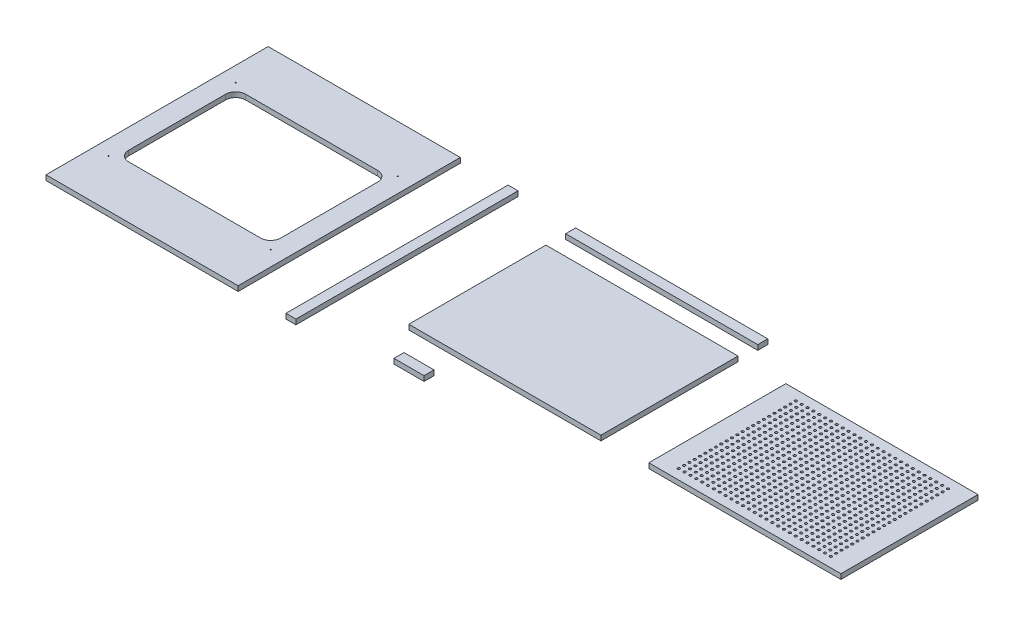
SolidWorks part; units mm, degrees
ref_plane "Front Plane" through (0, 0, 0) normal (0, 0, 1) x (1, 0, 0)
ref_plane "Top Plane" through (0, 0, 0) normal (0, 1, 0) x (1, 0, 0)
ref_plane "Right Plane" through (0, 0, 0) normal (1, 0, 0) x (0, 0, -1)
sketch "Sketch1" plane through (0, 0, 0) normal (0, 1, 0) x (1, 0, 0)
  line L0 (-192, -117) -> (192, -117)
  line L5 (-192, -222) -> (192, -222)
  line L6 (-192, -222) -> (-192, 222)
  line L7 (-192, 222) -> (192, 222)
  line L8 (192, -222) -> (192, 222)
  line L9 (-192, -222) -> (192, 222) construction
  line L10 (-192, 222) -> (192, -222) construction
  line L11 (192, 117) -> (-192, 117)
  line L12 (0, 117) -> (0, 222) construction
  line L13 (0, -117) -> (0, -222) construction
  line L14 (-152, 117) -> (-152, -117)
  line L15 (152, -117) -> (152, 117)
  line L16 (152, 0) -> (192, 0) construction
  line L17 (-152, 0) -> (-192, 0) construction
  line L18 (1292.7699, 155.8922) -> (908.7699, -118.1078) construction
  line L19 (-152, 117) -> (-162, 117) construction
  line L20 (-152, 117) -> (-152, 127) construction
  line L21 (-152, 127) -> (-162, 127) construction
  line L22 (-162, 117) -> (-162, 127) construction
  line L23 (813.2094, -118.1078) -> (429.2094, -118.1078)
  line L24 (813.2094, -118.1078) -> (813.2094, 155.8922)
  line L25 (813.2094, 155.8922) -> (429.2094, 155.8922)
  line L26 (429.2094, -118.1078) -> (429.2094, 155.8922)
  line L27 (813.2094, -118.1078) -> (429.2094, 155.8922) construction
  line L28 (813.2094, 155.8922) -> (429.2094, -118.1078) construction
  line L29 (287.48, 222) -> (307.48, 222)
  line L30 (287.48, 222) -> (287.48, -222)
  line L31 (287.48, -222) -> (307.48, -222)
  line L32 (307.48, 222) -> (307.48, -222)
  line L33 (429.2094, 195.3549) -> (813.2094, 195.3549)
  line L34 (429.2094, 195.3549) -> (429.2094, 215.3549)
  line L35 (429.2094, 215.3549) -> (813.2094, 215.3549)
  line L36 (813.2094, 195.3549) -> (813.2094, 215.3549)
  line L37 (473.4153, -171.9532) -> (533.4153, -171.9532)
  line L38 (473.4153, -171.9532) -> (473.4153, -191.9532)
  line L39 (473.4153, -191.9532) -> (533.4153, -191.9532)
  line L40 (533.4153, -171.9532) -> (533.4153, -191.9532)
  line L41 (908.7699, 155.8922) -> (1292.7699, 155.8922)
  line L42 (908.7699, 155.8922) -> (908.7699, -118.1078)
  line L43 (908.7699, -118.1078) -> (1292.7699, -118.1078)
  line L44 (1292.7699, 155.8922) -> (1292.7699, -118.1078)
  line L45 (908.7699, 155.8922) -> (1292.7699, -118.1078) construction
  line L46 (-162, -127) -> (0, -127) construction
  line L47 (0, -127) -> (0, 0) construction
  line L48 (-152, 0) -> (152, 0) construction
  line L49 (948.7699, 18.8922) -> (1252.7699, 18.8922) construction
  line L50 (948.7699, 135.8922) -> (948.7699, -98.1078) construction
  circle A0 centre (-162, 127) radius 1
  circle A1 centre (162, 127) radius 1
  circle A2 centre (162, -127) radius 1
  circle A3 centre (-162, -127) radius 1
  circle A4 centre (948.7699, -98.1078) radius 2.4
  circle A5 centre (960.4622, -98.1078) radius 2.4
  circle A6 centre (972.1545, -98.1078) radius 2.4
  circle A7 centre (983.8468, -98.1078) radius 2.4
  circle A8 centre (995.5391, -98.1078) radius 2.4
  circle A9 centre (1007.2314, -98.1078) radius 2.4
  circle A10 centre (1018.9237, -98.1078) radius 2.4
  circle A11 centre (1030.616, -98.1078) radius 2.4
  circle A12 centre (1042.3083, -98.1078) radius 2.4
  circle A13 centre (1054.0007, -98.1078) radius 2.4
  circle A14 centre (1065.693, -98.1078) radius 2.4
  circle A15 centre (1077.3853, -98.1078) radius 2.4
  circle A16 centre (1089.0776, -98.1078) radius 2.4
  circle A17 centre (1100.7699, -98.1078) radius 2.4
  circle A18 centre (1112.4622, -98.1078) radius 2.4
  circle A19 centre (1124.1545, -98.1078) radius 2.4
  circle A20 centre (1135.8468, -98.1078) radius 2.4
  circle A21 centre (1147.5391, -98.1078) radius 2.4
  circle A22 centre (1159.2314, -98.1078) radius 2.4
  circle A23 centre (1170.9237, -98.1078) radius 2.4
  circle A24 centre (1182.616, -98.1078) radius 2.4
  circle A25 centre (1194.3083, -98.1078) radius 2.4
  circle A26 centre (1206.0007, -98.1078) radius 2.4
  circle A27 centre (1217.693, -98.1078) radius 2.4
  circle A28 centre (1229.3853, -98.1078) radius 2.4
  circle A29 centre (1241.0776, -98.1078) radius 2.4
  circle A30 centre (1252.7699, -98.1078) radius 2.4
  circle A31 centre (960.4622, -87.4714) radius 2.4
  circle A32 centre (972.1545, -87.4714) radius 2.4
  circle A33 centre (983.8468, -87.4714) radius 2.4
  circle A34 centre (995.5391, -87.4714) radius 2.4
  circle A35 centre (1007.2314, -87.4714) radius 2.4
  circle A36 centre (1018.9237, -87.4714) radius 2.4
  circle A37 centre (1030.616, -87.4714) radius 2.4
  circle A38 centre (1042.3083, -87.4714) radius 2.4
  circle A39 centre (1054.0007, -87.4714) radius 2.4
  circle A40 centre (1065.693, -87.4714) radius 2.4
  circle A41 centre (1077.3853, -87.4714) radius 2.4
  circle A42 centre (1089.0776, -87.4714) radius 2.4
  circle A43 centre (1100.7699, -87.4714) radius 2.4
  circle A44 centre (1112.4622, -87.4714) radius 2.4
  circle A45 centre (1124.1545, -87.4714) radius 2.4
  circle A46 centre (1135.8468, -87.4714) radius 2.4
  circle A47 centre (1147.5391, -87.4714) radius 2.4
  circle A48 centre (1159.2314, -87.4714) radius 2.4
  circle A49 centre (1170.9237, -87.4714) radius 2.4
  circle A50 centre (1182.616, -87.4714) radius 2.4
  circle A51 centre (1194.3083, -87.4714) radius 2.4
  circle A52 centre (1206.0007, -87.4714) radius 2.4
  circle A53 centre (1217.693, -87.4714) radius 2.4
  circle A54 centre (1229.3853, -87.4714) radius 2.4
  circle A55 centre (1241.0776, -87.4714) radius 2.4
  circle A56 centre (1252.7699, -87.4714) radius 2.4
  circle A57 centre (960.4622, -76.835) radius 2.4
  circle A58 centre (972.1545, -76.835) radius 2.4
  circle A59 centre (983.8468, -76.835) radius 2.4
  circle A60 centre (995.5391, -76.835) radius 2.4
  circle A61 centre (1007.2314, -76.835) radius 2.4
  circle A62 centre (1018.9237, -76.835) radius 2.4
  circle A63 centre (1030.616, -76.835) radius 2.4
  circle A64 centre (1042.3083, -76.835) radius 2.4
  circle A65 centre (1054.0007, -76.835) radius 2.4
  circle A66 centre (1065.693, -76.835) radius 2.4
  circle A67 centre (1077.3853, -76.835) radius 2.4
  circle A68 centre (1089.0776, -76.835) radius 2.4
  circle A69 centre (1100.7699, -76.835) radius 2.4
  circle A70 centre (1112.4622, -76.835) radius 2.4
  circle A71 centre (1124.1545, -76.835) radius 2.4
  circle A72 centre (1135.8468, -76.835) radius 2.4
  circle A73 centre (1147.5391, -76.835) radius 2.4
  circle A74 centre (1159.2314, -76.835) radius 2.4
  circle A75 centre (1170.9237, -76.835) radius 2.4
  circle A76 centre (1182.616, -76.835) radius 2.4
  circle A77 centre (1194.3083, -76.835) radius 2.4
  circle A78 centre (1206.0007, -76.835) radius 2.4
  circle A79 centre (1217.693, -76.835) radius 2.4
  circle A80 centre (1229.3853, -76.835) radius 2.4
  circle A81 centre (1241.0776, -76.835) radius 2.4
  circle A82 centre (1252.7699, -76.835) radius 2.4
  circle A83 centre (960.4622, -66.1987) radius 2.4
  circle A84 centre (972.1545, -66.1987) radius 2.4
  circle A85 centre (983.8468, -66.1987) radius 2.4
  circle A86 centre (995.5391, -66.1987) radius 2.4
  circle A87 centre (1007.2314, -66.1987) radius 2.4
  circle A88 centre (1018.9237, -66.1987) radius 2.4
  circle A89 centre (1030.616, -66.1987) radius 2.4
  circle A90 centre (1042.3083, -66.1987) radius 2.4
  circle A91 centre (1054.0007, -66.1987) radius 2.4
  circle A92 centre (1065.693, -66.1987) radius 2.4
  circle A93 centre (1077.3853, -66.1987) radius 2.4
  circle A94 centre (1089.0776, -66.1987) radius 2.4
  circle A95 centre (1100.7699, -66.1987) radius 2.4
  circle A96 centre (1112.4622, -66.1987) radius 2.4
  circle A97 centre (1124.1545, -66.1987) radius 2.4
  circle A98 centre (1135.8468, -66.1987) radius 2.4
  circle A99 centre (1147.5391, -66.1987) radius 2.4
  circle A100 centre (1159.2314, -66.1987) radius 2.4
  circle A101 centre (1170.9237, -66.1987) radius 2.4
  circle A102 centre (1182.616, -66.1987) radius 2.4
  circle A103 centre (1194.3083, -66.1987) radius 2.4
  circle A104 centre (1206.0007, -66.1987) radius 2.4
  circle A105 centre (1217.693, -66.1987) radius 2.4
  circle A106 centre (1229.3853, -66.1987) radius 2.4
  circle A107 centre (1241.0776, -66.1987) radius 2.4
  circle A108 centre (1252.7699, -66.1987) radius 2.4
  circle A109 centre (960.4622, -55.5623) radius 2.4
  circle A110 centre (972.1545, -55.5623) radius 2.4
  circle A111 centre (983.8468, -55.5623) radius 2.4
  circle A112 centre (995.5391, -55.5623) radius 2.4
  circle A113 centre (1007.2314, -55.5623) radius 2.4
  circle A114 centre (1018.9237, -55.5623) radius 2.4
  circle A115 centre (1030.616, -55.5623) radius 2.4
  circle A116 centre (1042.3083, -55.5623) radius 2.4
  circle A117 centre (1054.0007, -55.5623) radius 2.4
  circle A118 centre (1065.693, -55.5623) radius 2.4
  circle A119 centre (1077.3853, -55.5623) radius 2.4
  circle A120 centre (1089.0776, -55.5623) radius 2.4
  circle A121 centre (1100.7699, -55.5623) radius 2.4
  circle A122 centre (1112.4622, -55.5623) radius 2.4
  circle A123 centre (1124.1545, -55.5623) radius 2.4
  circle A124 centre (1135.8468, -55.5623) radius 2.4
  circle A125 centre (1147.5391, -55.5623) radius 2.4
  circle A126 centre (1159.2314, -55.5623) radius 2.4
  circle A127 centre (1170.9237, -55.5623) radius 2.4
  circle A128 centre (1182.616, -55.5623) radius 2.4
  circle A129 centre (1194.3083, -55.5623) radius 2.4
  circle A130 centre (1206.0007, -55.5623) radius 2.4
  circle A131 centre (1217.693, -55.5623) radius 2.4
  circle A132 centre (1229.3853, -55.5623) radius 2.4
  circle A133 centre (1241.0776, -55.5623) radius 2.4
  circle A134 centre (1252.7699, -55.5623) radius 2.4
  circle A135 centre (960.4622, -44.9259) radius 2.4
  circle A136 centre (972.1545, -44.9259) radius 2.4
  circle A137 centre (983.8468, -44.9259) radius 2.4
  circle A138 centre (995.5391, -44.9259) radius 2.4
  circle A139 centre (1007.2314, -44.9259) radius 2.4
  circle A140 centre (1018.9237, -44.9259) radius 2.4
  circle A141 centre (1030.616, -44.9259) radius 2.4
  circle A142 centre (1042.3083, -44.9259) radius 2.4
  circle A143 centre (1054.0007, -44.9259) radius 2.4
  circle A144 centre (1065.693, -44.9259) radius 2.4
  circle A145 centre (1077.3853, -44.9259) radius 2.4
  circle A146 centre (1089.0776, -44.9259) radius 2.4
  circle A147 centre (1100.7699, -44.9259) radius 2.4
  circle A148 centre (1112.4622, -44.9259) radius 2.4
  circle A149 centre (1124.1545, -44.9259) radius 2.4
  circle A150 centre (1135.8468, -44.9259) radius 2.4
  circle A151 centre (1147.5391, -44.9259) radius 2.4
  circle A152 centre (1159.2314, -44.9259) radius 2.4
  circle A153 centre (1170.9237, -44.9259) radius 2.4
  circle A154 centre (1182.616, -44.9259) radius 2.4
  circle A155 centre (1194.3083, -44.9259) radius 2.4
  circle A156 centre (1206.0007, -44.9259) radius 2.4
  circle A157 centre (1217.693, -44.9259) radius 2.4
  circle A158 centre (1229.3853, -44.9259) radius 2.4
  circle A159 centre (1241.0776, -44.9259) radius 2.4
  circle A160 centre (1252.7699, -44.9259) radius 2.4
  circle A161 centre (960.4622, -34.2896) radius 2.4
  circle A162 centre (972.1545, -34.2896) radius 2.4
  circle A163 centre (983.8468, -34.2896) radius 2.4
  circle A164 centre (995.5391, -34.2896) radius 2.4
  circle A165 centre (1007.2314, -34.2896) radius 2.4
  circle A166 centre (1018.9237, -34.2896) radius 2.4
  circle A167 centre (1030.616, -34.2896) radius 2.4
  circle A168 centre (1042.3083, -34.2896) radius 2.4
  circle A169 centre (1054.0007, -34.2896) radius 2.4
  circle A170 centre (1065.693, -34.2896) radius 2.4
  circle A171 centre (1077.3853, -34.2896) radius 2.4
  circle A172 centre (1089.0776, -34.2896) radius 2.4
  circle A173 centre (1100.7699, -34.2896) radius 2.4
  circle A174 centre (1112.4622, -34.2896) radius 2.4
  circle A175 centre (1124.1545, -34.2896) radius 2.4
  circle A176 centre (1135.8468, -34.2896) radius 2.4
  circle A177 centre (1147.5391, -34.2896) radius 2.4
  circle A178 centre (1159.2314, -34.2896) radius 2.4
  circle A179 centre (1170.9237, -34.2896) radius 2.4
  circle A180 centre (1182.616, -34.2896) radius 2.4
  circle A181 centre (1194.3083, -34.2896) radius 2.4
  circle A182 centre (1206.0007, -34.2896) radius 2.4
  circle A183 centre (1217.693, -34.2896) radius 2.4
  circle A184 centre (1229.3853, -34.2896) radius 2.4
  circle A185 centre (1241.0776, -34.2896) radius 2.4
  circle A186 centre (1252.7699, -34.2896) radius 2.4
  circle A187 centre (960.4622, -23.6532) radius 2.4
  circle A188 centre (972.1545, -23.6532) radius 2.4
  circle A189 centre (983.8468, -23.6532) radius 2.4
  circle A190 centre (995.5391, -23.6532) radius 2.4
  circle A191 centre (1007.2314, -23.6532) radius 2.4
  circle A192 centre (1018.9237, -23.6532) radius 2.4
  circle A193 centre (1030.616, -23.6532) radius 2.4
  circle A194 centre (1042.3083, -23.6532) radius 2.4
  circle A195 centre (1054.0007, -23.6532) radius 2.4
  circle A196 centre (1065.693, -23.6532) radius 2.4
  circle A197 centre (1077.3853, -23.6532) radius 2.4
  circle A198 centre (1089.0776, -23.6532) radius 2.4
  circle A199 centre (1100.7699, -23.6532) radius 2.4
  circle A200 centre (1112.4622, -23.6532) radius 2.4
  circle A201 centre (1124.1545, -23.6532) radius 2.4
  circle A202 centre (1135.8468, -23.6532) radius 2.4
  circle A203 centre (1147.5391, -23.6532) radius 2.4
  circle A204 centre (1159.2314, -23.6532) radius 2.4
  circle A205 centre (1170.9237, -23.6532) radius 2.4
  circle A206 centre (1182.616, -23.6532) radius 2.4
  circle A207 centre (1194.3083, -23.6532) radius 2.4
  circle A208 centre (1206.0007, -23.6532) radius 2.4
  circle A209 centre (1217.693, -23.6532) radius 2.4
  circle A210 centre (1229.3853, -23.6532) radius 2.4
  circle A211 centre (1241.0776, -23.6532) radius 2.4
  circle A212 centre (1252.7699, -23.6532) radius 2.4
  circle A213 centre (960.4622, -13.0169) radius 2.4
  circle A214 centre (972.1545, -13.0169) radius 2.4
  circle A215 centre (983.8468, -13.0169) radius 2.4
  circle A216 centre (995.5391, -13.0169) radius 2.4
  circle A217 centre (1007.2314, -13.0169) radius 2.4
  circle A218 centre (1018.9237, -13.0169) radius 2.4
  circle A219 centre (1030.616, -13.0169) radius 2.4
  circle A220 centre (1042.3083, -13.0169) radius 2.4
  circle A221 centre (1054.0007, -13.0169) radius 2.4
  circle A222 centre (1065.693, -13.0169) radius 2.4
  circle A223 centre (1077.3853, -13.0169) radius 2.4
  circle A224 centre (1089.0776, -13.0169) radius 2.4
  circle A225 centre (1100.7699, -13.0169) radius 2.4
  circle A226 centre (1112.4622, -13.0169) radius 2.4
  circle A227 centre (1124.1545, -13.0169) radius 2.4
  circle A228 centre (1135.8468, -13.0169) radius 2.4
  circle A229 centre (1147.5391, -13.0169) radius 2.4
  circle A230 centre (1159.2314, -13.0169) radius 2.4
  circle A231 centre (1170.9237, -13.0169) radius 2.4
  circle A232 centre (1182.616, -13.0169) radius 2.4
  circle A233 centre (1194.3083, -13.0169) radius 2.4
  circle A234 centre (1206.0007, -13.0169) radius 2.4
  circle A235 centre (1217.693, -13.0169) radius 2.4
  circle A236 centre (1229.3853, -13.0169) radius 2.4
  circle A237 centre (1241.0776, -13.0169) radius 2.4
  circle A238 centre (1252.7699, -13.0169) radius 2.4
  circle A239 centre (960.4622, -2.3805) radius 2.4
  circle A240 centre (972.1545, -2.3805) radius 2.4
  circle A241 centre (983.8468, -2.3805) radius 2.4
  circle A242 centre (995.5391, -2.3805) radius 2.4
  circle A243 centre (1007.2314, -2.3805) radius 2.4
  circle A244 centre (1018.9237, -2.3805) radius 2.4
  circle A245 centre (1030.616, -2.3805) radius 2.4
  circle A246 centre (1042.3083, -2.3805) radius 2.4
  circle A247 centre (1054.0007, -2.3805) radius 2.4
  circle A248 centre (1065.693, -2.3805) radius 2.4
  circle A249 centre (1077.3853, -2.3805) radius 2.4
  circle A250 centre (1089.0776, -2.3805) radius 2.4
  circle A251 centre (1100.7699, -2.3805) radius 2.4
  circle A252 centre (1112.4622, -2.3805) radius 2.4
  circle A253 centre (1124.1545, -2.3805) radius 2.4
  circle A254 centre (1135.8468, -2.3805) radius 2.4
  circle A255 centre (1147.5391, -2.3805) radius 2.4
  circle A256 centre (1159.2314, -2.3805) radius 2.4
  circle A257 centre (1170.9237, -2.3805) radius 2.4
  circle A258 centre (1182.616, -2.3805) radius 2.4
  circle A259 centre (1194.3083, -2.3805) radius 2.4
  circle A260 centre (1206.0007, -2.3805) radius 2.4
  circle A261 centre (1217.693, -2.3805) radius 2.4
  circle A262 centre (1229.3853, -2.3805) radius 2.4
  circle A263 centre (1241.0776, -2.3805) radius 2.4
  circle A264 centre (1252.7699, -2.3805) radius 2.4
  circle A265 centre (960.4622, 8.2559) radius 2.4
  circle A266 centre (972.1545, 8.2559) radius 2.4
  circle A267 centre (983.8468, 8.2559) radius 2.4
  circle A268 centre (995.5391, 8.2559) radius 2.4
  circle A269 centre (1007.2314, 8.2559) radius 2.4
  circle A270 centre (1018.9237, 8.2559) radius 2.4
  circle A271 centre (1030.616, 8.2559) radius 2.4
  circle A272 centre (1042.3083, 8.2559) radius 2.4
  circle A273 centre (1054.0007, 8.2559) radius 2.4
  circle A274 centre (1065.693, 8.2559) radius 2.4
  circle A275 centre (1077.3853, 8.2559) radius 2.4
  circle A276 centre (1089.0776, 8.2559) radius 2.4
  circle A277 centre (1100.7699, 8.2559) radius 2.4
  circle A278 centre (1112.4622, 8.2559) radius 2.4
  circle A279 centre (1124.1545, 8.2559) radius 2.4
  circle A280 centre (1135.8468, 8.2559) radius 2.4
  circle A281 centre (1147.5391, 8.2559) radius 2.4
  circle A282 centre (1159.2314, 8.2559) radius 2.4
  circle A283 centre (1170.9237, 8.2559) radius 2.4
  circle A284 centre (1182.616, 8.2559) radius 2.4
  circle A285 centre (1194.3083, 8.2559) radius 2.4
  circle A286 centre (1206.0007, 8.2559) radius 2.4
  circle A287 centre (1217.693, 8.2559) radius 2.4
  circle A288 centre (1229.3853, 8.2559) radius 2.4
  circle A289 centre (1241.0776, 8.2559) radius 2.4
  circle A290 centre (1252.7699, 8.2559) radius 2.4
  circle A291 centre (960.4622, 18.8922) radius 2.4
  circle A292 centre (972.1545, 18.8922) radius 2.4
  circle A293 centre (983.8468, 18.8922) radius 2.4
  circle A294 centre (995.5391, 18.8922) radius 2.4
  circle A295 centre (1007.2314, 18.8922) radius 2.4
  circle A296 centre (1018.9237, 18.8922) radius 2.4
  circle A297 centre (1030.616, 18.8922) radius 2.4
  circle A298 centre (1042.3083, 18.8922) radius 2.4
  circle A299 centre (1054.0007, 18.8922) radius 2.4
  circle A300 centre (1065.693, 18.8922) radius 2.4
  circle A301 centre (1077.3853, 18.8922) radius 2.4
  circle A302 centre (1089.0776, 18.8922) radius 2.4
  circle A303 centre (1100.7699, 18.8922) radius 2.4
  circle A304 centre (1112.4622, 18.8922) radius 2.4
  circle A305 centre (1124.1545, 18.8922) radius 2.4
  circle A306 centre (1135.8468, 18.8922) radius 2.4
  circle A307 centre (1147.5391, 18.8922) radius 2.4
  circle A308 centre (1159.2314, 18.8922) radius 2.4
  circle A309 centre (1170.9237, 18.8922) radius 2.4
  circle A310 centre (1182.616, 18.8922) radius 2.4
  circle A311 centre (1194.3083, 18.8922) radius 2.4
  circle A312 centre (1206.0007, 18.8922) radius 2.4
  circle A313 centre (1217.693, 18.8922) radius 2.4
  circle A314 centre (1229.3853, 18.8922) radius 2.4
  circle A315 centre (1241.0776, 18.8922) radius 2.4
  circle A316 centre (1252.7699, 18.8922) radius 2.4
  circle A317 centre (960.4622, 29.5286) radius 2.4
  circle A318 centre (972.1545, 29.5286) radius 2.4
  circle A319 centre (983.8468, 29.5286) radius 2.4
  circle A320 centre (995.5391, 29.5286) radius 2.4
  circle A321 centre (1007.2314, 29.5286) radius 2.4
  circle A322 centre (1018.9237, 29.5286) radius 2.4
  circle A323 centre (1030.616, 29.5286) radius 2.4
  circle A324 centre (1042.3083, 29.5286) radius 2.4
  circle A325 centre (1054.0007, 29.5286) radius 2.4
  circle A326 centre (1065.693, 29.5286) radius 2.4
  circle A327 centre (1077.3853, 29.5286) radius 2.4
  circle A328 centre (1089.0776, 29.5286) radius 2.4
  circle A329 centre (1100.7699, 29.5286) radius 2.4
  circle A330 centre (1112.4622, 29.5286) radius 2.4
  circle A331 centre (1124.1545, 29.5286) radius 2.4
  circle A332 centre (1135.8468, 29.5286) radius 2.4
  circle A333 centre (1147.5391, 29.5286) radius 2.4
  circle A334 centre (1159.2314, 29.5286) radius 2.4
  circle A335 centre (1170.9237, 29.5286) radius 2.4
  circle A336 centre (1182.616, 29.5286) radius 2.4
  circle A337 centre (1194.3083, 29.5286) radius 2.4
  circle A338 centre (1206.0007, 29.5286) radius 2.4
  circle A339 centre (1217.693, 29.5286) radius 2.4
  circle A340 centre (1229.3853, 29.5286) radius 2.4
  circle A341 centre (1241.0776, 29.5286) radius 2.4
  circle A342 centre (1252.7699, 29.5286) radius 2.4
  circle A343 centre (960.4622, 40.165) radius 2.4
  circle A344 centre (972.1545, 40.165) radius 2.4
  circle A345 centre (983.8468, 40.165) radius 2.4
  circle A346 centre (995.5391, 40.165) radius 2.4
  circle A347 centre (1007.2314, 40.165) radius 2.4
  circle A348 centre (1018.9237, 40.165) radius 2.4
  circle A349 centre (1030.616, 40.165) radius 2.4
  circle A350 centre (1042.3083, 40.165) radius 2.4
  circle A351 centre (1054.0007, 40.165) radius 2.4
  circle A352 centre (1065.693, 40.165) radius 2.4
  circle A353 centre (1077.3853, 40.165) radius 2.4
  circle A354 centre (1089.0776, 40.165) radius 2.4
  circle A355 centre (1100.7699, 40.165) radius 2.4
  circle A356 centre (1112.4622, 40.165) radius 2.4
  circle A357 centre (1124.1545, 40.165) radius 2.4
  circle A358 centre (1135.8468, 40.165) radius 2.4
  circle A359 centre (1147.5391, 40.165) radius 2.4
  circle A360 centre (1159.2314, 40.165) radius 2.4
  circle A361 centre (1170.9237, 40.165) radius 2.4
  circle A362 centre (1182.616, 40.165) radius 2.4
  circle A363 centre (1194.3083, 40.165) radius 2.4
  circle A364 centre (1206.0007, 40.165) radius 2.4
  circle A365 centre (1217.693, 40.165) radius 2.4
  circle A366 centre (1229.3853, 40.165) radius 2.4
  circle A367 centre (1241.0776, 40.165) radius 2.4
  circle A368 centre (1252.7699, 40.165) radius 2.4
  circle A369 centre (960.4622, 50.8013) radius 2.4
  circle A370 centre (972.1545, 50.8013) radius 2.4
  circle A371 centre (983.8468, 50.8013) radius 2.4
  circle A372 centre (995.5391, 50.8013) radius 2.4
  circle A373 centre (1007.2314, 50.8013) radius 2.4
  circle A374 centre (1018.9237, 50.8013) radius 2.4
  circle A375 centre (1030.616, 50.8013) radius 2.4
  circle A376 centre (1042.3083, 50.8013) radius 2.4
  circle A377 centre (1054.0007, 50.8013) radius 2.4
  circle A378 centre (1065.693, 50.8013) radius 2.4
  circle A379 centre (1077.3853, 50.8013) radius 2.4
  circle A380 centre (1089.0776, 50.8013) radius 2.4
  circle A381 centre (1100.7699, 50.8013) radius 2.4
  circle A382 centre (1112.4622, 50.8013) radius 2.4
  circle A383 centre (1124.1545, 50.8013) radius 2.4
  circle A384 centre (1135.8468, 50.8013) radius 2.4
  circle A385 centre (1147.5391, 50.8013) radius 2.4
  circle A386 centre (1159.2314, 50.8013) radius 2.4
  circle A387 centre (1170.9237, 50.8013) radius 2.4
  circle A388 centre (1182.616, 50.8013) radius 2.4
  circle A389 centre (1194.3083, 50.8013) radius 2.4
  circle A390 centre (1206.0007, 50.8013) radius 2.4
  circle A391 centre (1217.693, 50.8013) radius 2.4
  circle A392 centre (1229.3853, 50.8013) radius 2.4
  circle A393 centre (1241.0776, 50.8013) radius 2.4
  circle A394 centre (1252.7699, 50.8013) radius 2.4
  circle A395 centre (960.4622, 61.4377) radius 2.4
  circle A396 centre (972.1545, 61.4377) radius 2.4
  circle A397 centre (983.8468, 61.4377) radius 2.4
  circle A398 centre (995.5391, 61.4377) radius 2.4
  circle A399 centre (1007.2314, 61.4377) radius 2.4
  circle A400 centre (1018.9237, 61.4377) radius 2.4
  circle A401 centre (1030.616, 61.4377) radius 2.4
  circle A402 centre (1042.3083, 61.4377) radius 2.4
  circle A403 centre (1054.0007, 61.4377) radius 2.4
  circle A404 centre (1065.693, 61.4377) radius 2.4
  circle A405 centre (1077.3853, 61.4377) radius 2.4
  circle A406 centre (1089.0776, 61.4377) radius 2.4
  circle A407 centre (1100.7699, 61.4377) radius 2.4
  circle A408 centre (1112.4622, 61.4377) radius 2.4
  circle A409 centre (1124.1545, 61.4377) radius 2.4
  circle A410 centre (1135.8468, 61.4377) radius 2.4
  circle A411 centre (1147.5391, 61.4377) radius 2.4
  circle A412 centre (1159.2314, 61.4377) radius 2.4
  circle A413 centre (1170.9237, 61.4377) radius 2.4
  circle A414 centre (1182.616, 61.4377) radius 2.4
  circle A415 centre (1194.3083, 61.4377) radius 2.4
  circle A416 centre (1206.0007, 61.4377) radius 2.4
  circle A417 centre (1217.693, 61.4377) radius 2.4
  circle A418 centre (1229.3853, 61.4377) radius 2.4
  circle A419 centre (1241.0776, 61.4377) radius 2.4
  circle A420 centre (1252.7699, 61.4377) radius 2.4
  circle A421 centre (960.4622, 72.0741) radius 2.4
  circle A422 centre (972.1545, 72.0741) radius 2.4
  circle A423 centre (983.8468, 72.0741) radius 2.4
  circle A424 centre (995.5391, 72.0741) radius 2.4
  circle A425 centre (1007.2314, 72.0741) radius 2.4
  circle A426 centre (1018.9237, 72.0741) radius 2.4
  circle A427 centre (1030.616, 72.0741) radius 2.4
  circle A428 centre (1042.3083, 72.0741) radius 2.4
  circle A429 centre (1054.0007, 72.0741) radius 2.4
  circle A430 centre (1065.693, 72.0741) radius 2.4
  circle A431 centre (1077.3853, 72.0741) radius 2.4
  circle A432 centre (1089.0776, 72.0741) radius 2.4
  circle A433 centre (1100.7699, 72.0741) radius 2.4
  circle A434 centre (1112.4622, 72.0741) radius 2.4
  circle A435 centre (1124.1545, 72.0741) radius 2.4
  circle A436 centre (1135.8468, 72.0741) radius 2.4
  circle A437 centre (1147.5391, 72.0741) radius 2.4
  circle A438 centre (1159.2314, 72.0741) radius 2.4
  circle A439 centre (1170.9237, 72.0741) radius 2.4
  circle A440 centre (1182.616, 72.0741) radius 2.4
  circle A441 centre (1194.3083, 72.0741) radius 2.4
  circle A442 centre (1206.0007, 72.0741) radius 2.4
  circle A443 centre (1217.693, 72.0741) radius 2.4
  circle A444 centre (1229.3853, 72.0741) radius 2.4
  circle A445 centre (1241.0776, 72.0741) radius 2.4
  circle A446 centre (1252.7699, 72.0741) radius 2.4
  circle A447 centre (960.4622, 82.7104) radius 2.4
  circle A448 centre (972.1545, 82.7104) radius 2.4
  circle A449 centre (983.8468, 82.7104) radius 2.4
  circle A450 centre (995.5391, 82.7104) radius 2.4
  circle A451 centre (1007.2314, 82.7104) radius 2.4
  circle A452 centre (1018.9237, 82.7104) radius 2.4
  circle A453 centre (1030.616, 82.7104) radius 2.4
  circle A454 centre (1042.3083, 82.7104) radius 2.4
  circle A455 centre (1054.0007, 82.7104) radius 2.4
  circle A456 centre (1065.693, 82.7104) radius 2.4
  circle A457 centre (1077.3853, 82.7104) radius 2.4
  circle A458 centre (1089.0776, 82.7104) radius 2.4
  circle A459 centre (1100.7699, 82.7104) radius 2.4
  circle A460 centre (1112.4622, 82.7104) radius 2.4
  circle A461 centre (1124.1545, 82.7104) radius 2.4
  circle A462 centre (1135.8468, 82.7104) radius 2.4
  circle A463 centre (1147.5391, 82.7104) radius 2.4
  circle A464 centre (1159.2314, 82.7104) radius 2.4
  circle A465 centre (1170.9237, 82.7104) radius 2.4
  circle A466 centre (1182.616, 82.7104) radius 2.4
  circle A467 centre (1194.3083, 82.7104) radius 2.4
  circle A468 centre (1206.0007, 82.7104) radius 2.4
  circle A469 centre (1217.693, 82.7104) radius 2.4
  circle A470 centre (1229.3853, 82.7104) radius 2.4
  circle A471 centre (1241.0776, 82.7104) radius 2.4
  circle A472 centre (1252.7699, 82.7104) radius 2.4
  circle A473 centre (960.4622, 93.3468) radius 2.4
  circle A474 centre (972.1545, 93.3468) radius 2.4
  circle A475 centre (983.8468, 93.3468) radius 2.4
  circle A476 centre (995.5391, 93.3468) radius 2.4
  circle A477 centre (1007.2314, 93.3468) radius 2.4
  circle A478 centre (1018.9237, 93.3468) radius 2.4
  circle A479 centre (1030.616, 93.3468) radius 2.4
  circle A480 centre (1042.3083, 93.3468) radius 2.4
  circle A481 centre (1054.0007, 93.3468) radius 2.4
  circle A482 centre (1065.693, 93.3468) radius 2.4
  circle A483 centre (1077.3853, 93.3468) radius 2.4
  circle A484 centre (1089.0776, 93.3468) radius 2.4
  circle A485 centre (1100.7699, 93.3468) radius 2.4
  circle A486 centre (1112.4622, 93.3468) radius 2.4
  circle A487 centre (1124.1545, 93.3468) radius 2.4
  circle A488 centre (1135.8468, 93.3468) radius 2.4
  circle A489 centre (1147.5391, 93.3468) radius 2.4
  circle A490 centre (1159.2314, 93.3468) radius 2.4
  circle A491 centre (1170.9237, 93.3468) radius 2.4
  circle A492 centre (1182.616, 93.3468) radius 2.4
  circle A493 centre (1194.3083, 93.3468) radius 2.4
  circle A494 centre (1206.0007, 93.3468) radius 2.4
  circle A495 centre (1217.693, 93.3468) radius 2.4
  circle A496 centre (1229.3853, 93.3468) radius 2.4
  circle A497 centre (1241.0776, 93.3468) radius 2.4
  circle A498 centre (1252.7699, 93.3468) radius 2.4
  circle A499 centre (960.4622, 103.9831) radius 2.4
  circle A500 centre (972.1545, 103.9831) radius 2.4
  circle A501 centre (983.8468, 103.9831) radius 2.4
  circle A502 centre (995.5391, 103.9831) radius 2.4
  circle A503 centre (1007.2314, 103.9831) radius 2.4
  circle A504 centre (1018.9237, 103.9831) radius 2.4
  circle A505 centre (1030.616, 103.9831) radius 2.4
  circle A506 centre (1042.3083, 103.9831) radius 2.4
  circle A507 centre (1054.0007, 103.9831) radius 2.4
  circle A508 centre (1065.693, 103.9831) radius 2.4
  circle A509 centre (1077.3853, 103.9831) radius 2.4
  circle A510 centre (1089.0776, 103.9831) radius 2.4
  circle A511 centre (1100.7699, 103.9831) radius 2.4
  circle A512 centre (1112.4622, 103.9831) radius 2.4
  circle A513 centre (1124.1545, 103.9831) radius 2.4
  circle A514 centre (1135.8468, 103.9831) radius 2.4
  circle A515 centre (1147.5391, 103.9831) radius 2.4
  circle A516 centre (1159.2314, 103.9831) radius 2.4
  circle A517 centre (1170.9237, 103.9831) radius 2.4
  circle A518 centre (1182.616, 103.9831) radius 2.4
  circle A519 centre (1194.3083, 103.9831) radius 2.4
  circle A520 centre (1206.0007, 103.9831) radius 2.4
  circle A521 centre (1217.693, 103.9831) radius 2.4
  circle A522 centre (1229.3853, 103.9831) radius 2.4
  circle A523 centre (1241.0776, 103.9831) radius 2.4
  circle A524 centre (1252.7699, 103.9831) radius 2.4
  circle A525 centre (960.4622, 114.6195) radius 2.4
  circle A526 centre (972.1545, 114.6195) radius 2.4
  circle A527 centre (983.8468, 114.6195) radius 2.4
  circle A528 centre (995.5391, 114.6195) radius 2.4
  circle A529 centre (1007.2314, 114.6195) radius 2.4
  circle A530 centre (1018.9237, 114.6195) radius 2.4
  circle A531 centre (1030.616, 114.6195) radius 2.4
  circle A532 centre (1042.3083, 114.6195) radius 2.4
  circle A533 centre (1054.0007, 114.6195) radius 2.4
  circle A534 centre (1065.693, 114.6195) radius 2.4
  circle A535 centre (1077.3853, 114.6195) radius 2.4
  circle A536 centre (1089.0776, 114.6195) radius 2.4
  circle A537 centre (1100.7699, 114.6195) radius 2.4
  circle A538 centre (1112.4622, 114.6195) radius 2.4
  circle A539 centre (1124.1545, 114.6195) radius 2.4
  circle A540 centre (1135.8468, 114.6195) radius 2.4
  circle A541 centre (1147.5391, 114.6195) radius 2.4
  circle A542 centre (1159.2314, 114.6195) radius 2.4
  circle A543 centre (1170.9237, 114.6195) radius 2.4
  circle A544 centre (1182.616, 114.6195) radius 2.4
  circle A545 centre (1194.3083, 114.6195) radius 2.4
  circle A546 centre (1206.0007, 114.6195) radius 2.4
  circle A547 centre (1217.693, 114.6195) radius 2.4
  circle A548 centre (1229.3853, 114.6195) radius 2.4
  circle A549 centre (1241.0776, 114.6195) radius 2.4
  circle A550 centre (1252.7699, 114.6195) radius 2.4
  circle A551 centre (960.4622, 125.2559) radius 2.4
  circle A552 centre (972.1545, 125.2559) radius 2.4
  circle A553 centre (983.8468, 125.2559) radius 2.4
  circle A554 centre (995.5391, 125.2559) radius 2.4
  circle A555 centre (1007.2314, 125.2559) radius 2.4
  circle A556 centre (1018.9237, 125.2559) radius 2.4
  circle A557 centre (1030.616, 125.2559) radius 2.4
  circle A558 centre (1042.3083, 125.2559) radius 2.4
  circle A559 centre (1054.0007, 125.2559) radius 2.4
  circle A560 centre (1065.693, 125.2559) radius 2.4
  circle A561 centre (1077.3853, 125.2559) radius 2.4
  circle A562 centre (1089.0776, 125.2559) radius 2.4
  circle A563 centre (1100.7699, 125.2559) radius 2.4
  circle A564 centre (1112.4622, 125.2559) radius 2.4
  circle A565 centre (1124.1545, 125.2559) radius 2.4
  circle A566 centre (1135.8468, 125.2559) radius 2.4
  circle A567 centre (1147.5391, 125.2559) radius 2.4
  circle A568 centre (1159.2314, 125.2559) radius 2.4
  circle A569 centre (1170.9237, 125.2559) radius 2.4
  circle A570 centre (1182.616, 125.2559) radius 2.4
  circle A571 centre (1194.3083, 125.2559) radius 2.4
  circle A572 centre (1206.0007, 125.2559) radius 2.4
  circle A573 centre (1217.693, 125.2559) radius 2.4
  circle A574 centre (1229.3853, 125.2559) radius 2.4
  circle A575 centre (1241.0776, 125.2559) radius 2.4
  circle A576 centre (1252.7699, 125.2559) radius 2.4
  circle A577 centre (960.4622, 135.8922) radius 2.4
  circle A578 centre (972.1545, 135.8922) radius 2.4
  circle A579 centre (983.8468, 135.8922) radius 2.4
  circle A580 centre (995.5391, 135.8922) radius 2.4
  circle A581 centre (1007.2314, 135.8922) radius 2.4
  circle A582 centre (1018.9237, 135.8922) radius 2.4
  circle A583 centre (1030.616, 135.8922) radius 2.4
  circle A584 centre (1042.3083, 135.8922) radius 2.4
  circle A585 centre (1054.0007, 135.8922) radius 2.4
  circle A586 centre (1065.693, 135.8922) radius 2.4
  circle A587 centre (1077.3853, 135.8922) radius 2.4
  circle A588 centre (1089.0776, 135.8922) radius 2.4
  circle A589 centre (1100.7699, 135.8922) radius 2.4
  circle A590 centre (1112.4622, 135.8922) radius 2.4
  circle A591 centre (1124.1545, 135.8922) radius 2.4
  circle A592 centre (1135.8468, 135.8922) radius 2.4
  circle A593 centre (1147.5391, 135.8922) radius 2.4
  circle A594 centre (1159.2314, 135.8922) radius 2.4
  circle A595 centre (1170.9237, 135.8922) radius 2.4
  circle A596 centre (1182.616, 135.8922) radius 2.4
  circle A597 centre (1194.3083, 135.8922) radius 2.4
  circle A598 centre (1206.0007, 135.8922) radius 2.4
  circle A599 centre (1217.693, 135.8922) radius 2.4
  circle A600 centre (1229.3853, 135.8922) radius 2.4
  circle A601 centre (1241.0776, 135.8922) radius 2.4
  circle A602 centre (1252.7699, 135.8922) radius 2.4
  circle A603 centre (948.7699, -87.4714) radius 2.4
  circle A604 centre (948.7699, -76.835) radius 2.4
  circle A605 centre (948.7699, -66.1987) radius 2.4
  circle A606 centre (948.7699, -55.5623) radius 2.4
  circle A607 centre (948.7699, -44.9259) radius 2.4
  circle A608 centre (948.7699, -34.2896) radius 2.4
  circle A609 centre (948.7699, -23.6532) radius 2.4
  circle A610 centre (948.7699, -13.0169) radius 2.4
  circle A611 centre (948.7699, -2.3805) radius 2.4
  circle A612 centre (948.7699, 8.2559) radius 2.4
  circle A613 centre (948.7699, 18.8922) radius 2.4
  circle A614 centre (948.7699, 29.5286) radius 2.4
  circle A615 centre (948.7699, 40.165) radius 2.4
  circle A616 centre (948.7699, 50.8013) radius 2.4
  circle A617 centre (948.7699, 61.4377) radius 2.4
  circle A618 centre (948.7699, 72.0741) radius 2.4
  circle A619 centre (948.7699, 82.7104) radius 2.4
  circle A620 centre (948.7699, 93.3468) radius 2.4
  circle A621 centre (948.7699, 103.9831) radius 2.4
  circle A622 centre (948.7699, 114.6195) radius 2.4
  circle A623 centre (948.7699, 125.2559) radius 2.4
  circle A624 centre (948.7699, 135.8922) radius 2.4
  point P0 (0, 0)
  point P5 (621.2094, 18.8922)
  point P58 (1100.7699, 18.8922)
  point P59 (0, 0)
  point P62 (948.7699, 18.8922)
  point P63 (0, 0)
  dimension "D6" = 2
  dimension "D11" = 4.8
  dimension "D1" = 384
  dimension "D2" = 444
  dimension "D3" = 105
  dimension "D4" = 40
  dimension "D5" = 10
  dimension "D7" = 234
  dimension "D8" = 274
  dimension "D9" = 20
  dimension "D10" = 60
  dimension "D12" = 27
  dimension "D13" = 23
extrude "Boss-Extrude1" add sketch "Sketch1" along normal blind 10 contours L11 L8 L7 L6 A0 A1 | L14 L11 L6 L0 | L5 L8 L0 L6 A2 A3 | L15 L0 L8 L11 | L44 L41 L42 L43 A624 A623 A622 A621 A620 A619 A618 A617 A616 A615 A614 A613 A612 A611 A610 A609 A608 A607 A606 A605 A604 A603 A602 | L26 L23 L24 L25 | L33 L36 L35 L34 | L40 L37 L38 L39 | L32 L29 L30 L31 region at (-172, 0, 0) region at (0, 0, 169.5066) region at (0, 0, -169.5066) region at (172, 0, 0) region at (621.2094, 0, -18.8922) region at (297.48, 0, 0) region at (621.2094, 0, -205.3549) region at (503.4153, 0, 181.9532) region at (1100.7699, 0, -151.1749)
fillet "Fillet1" radius 20 4 edges at (-152, 5, 117) (152, 5, 117) (152, 5, -117) (-152, 5, -117)
